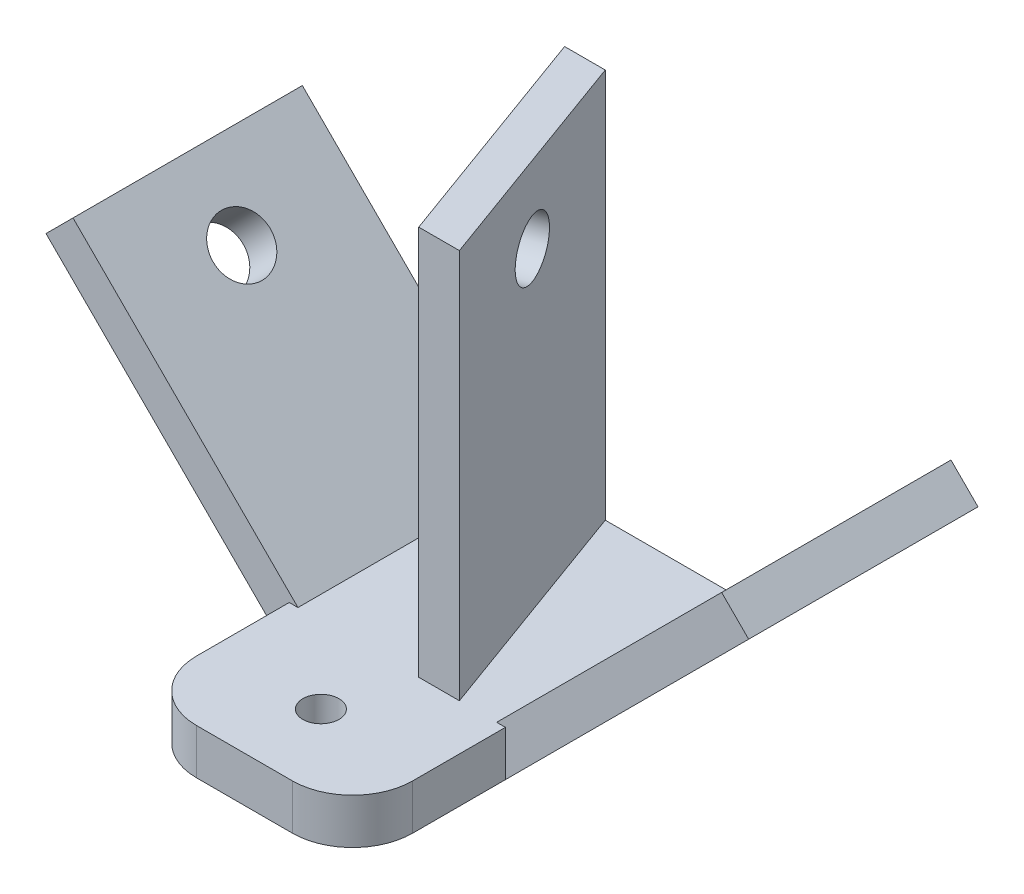
SolidWorks part; units mm, degrees
ref_plane "Front Plane" through (0, 0, 0) normal (0, 0, 1) x (1, 0, 0)
ref_plane "Top Plane" through (0, 0, 0) normal (0, 1, 0) x (1, 0, 0)
ref_plane "Right Plane" through (0, 0, 0) normal (1, 0, 0) x (0, 0, -1)
sketch "Sketch1" plane through (0, 0, 0) normal (0, 0, 1) x (1, 0, 0)
  line L0 (-53.8815, 53.8815) -> (0, 0)
  line L1 (0, 0) -> (53.8815, 53.8815)
  line L2 (53.8815, 53.8815) -> (58.3717, 49.3914)
  line L3 (58.3717, 49.3914) -> (0, -8.9803)
  line L4 (0, -8.9803) -> (-58.3717, 49.3914)
  line L5 (-58.3717, 49.3914) -> (-53.8815, 53.8815)
  line L6 (0, -8.9803) -> (0, 0) construction
  dimension "D1" = 6.35
  dimension "D2" = 76.2
extrude "Boss-Extrude1" add sketch "Sketch1" along normal mid plane 38.1
sketch "Sketch2" plane through (0, 0, 0) normal (0, 1, 0) x (1, 0, 0)
  line L0 (-10.3124, 19.05) -> (-3.5549, 19.05)
  line L1 (0, 19.05) -> (-53.8815, 19.05) construction
  line L2 (-3.5549, 19.05) -> (10.3124, -19.05)
  line L3 (53.8815, -19.05) -> (0, -19.05) construction
  line L4 (10.3124, -19.05) -> (3.5549, -19.05)
  line L5 (3.5549, -19.05) -> (-10.3124, 19.05)
  line L6 (-6.9336, 19.05) -> (6.9336, -19.05) construction
  line L7 (0, -19.05) -> (-53.8815, -19.05) construction
  point P10 (0, 0)
  dimension "D1" = 6.35
  dimension "D2" = 70
extrude "Boss-Extrude2" add sketch "Sketch2" against normal up to body and the other way blind 76.2 from offset 5.08 separate body
sketch "Sketch3" plane through (-4.4901, -4.4901, 0) normal (-0.7071, -0.7071, 0) x (0, 0, 1)
  line L0 (19.05, 76.2) -> (-19.05, 76.2) construction
  circle A0 centre (0, 63.5) radius 4.7625
  point P4 (0, 76.2)
  dimension "D1" = 9.525
  dimension "D2" = 12.7
extrude "Cut-Extrude1" cut sketch "Sketch3" against normal up to next
mirror "Mirror1" about plane through (0, 0, 0) normal (1, 0, 0) of "Cut-Extrude1"
sketch "Sketch4" plane through (2.9835, 0, -1.0859) normal (0.9397, 0, -0.342) x (-0.342, 0, -0.9397)
  line L0 (-21.4282, 81.28) -> (19.117, 81.28) construction
  circle A0 centre (-1.1556, 68.58) radius 4.7625
  point P4 (-1.1556, 81.28)
  dimension "D2" = 9.525
  dimension "D1" = 12.7
extrude "Cut-Extrude2" cut sketch "Sketch4" against normal up to next
sketch "Sketch5" plane through (0, 0, 19.05) normal (0, 0, 1) x (1, 0, 0)
  line L0 (-16.51, 16.51) -> (16.51, 16.51)
  line L1 (0, 0) -> (-53.8815, 53.8815) construction
  line L2 (53.8815, 53.8815) -> (10.3124, 10.3124) construction
  line L3 (16.51, 16.51) -> (0, 0)
  line L4 (0, 0) -> (-16.51, 16.51)
  dimension "D1" = 16.51
extrude "Boss-Extrude3" add sketch "Sketch5" against normal up to surface (38.1 mm away) up to face at (-2.7735, 37.3993, -19.05)
chamfer "Chamfer1" distance 25.4 angle 45 1 edges at (0, -8.9803, 0)
sketch "Sketch6" plane through (0, 8.9803, 0) normal (0, -1, 0) x (1, 0, 0)
  line L1 (-17.9605, 19.05) -> (17.9605, 19.05)
  line L2 (-17.9605, 19.05) -> (-17.9605, 44.45)
  line L3 (-17.9605, 44.45) -> (17.9605, 44.45)
  line L4 (17.9605, 19.05) -> (17.9605, 44.45)
  line L5 (-17.9605, 19.05) -> (17.9605, 44.45) construction
  line L6 (-17.9605, 44.45) -> (17.9605, 19.05) construction
  point P4 (0, 31.75)
  dimension "D1" = 25.4
extrude "Boss-Extrude4" add sketch "Sketch6" against normal up to surface (7.5297 mm away) up to face at (-9.9444, 16.51, 0)
sketch "Sketch7" plane through (0, 16.51, 0) normal (0, 1, 0) x (1, 0, 0)
  line L0 (-17.9605, -44.45) -> (-17.9605, -19.05) construction
  line L1 (17.9605, -44.45) -> (-17.9605, -44.45) construction
  circle A0 centre (0, -31.75) radius 3
  point P4 (-17.9605, -31.75)
  point P7 (0, -44.45)
  dimension "D1" = 6
extrude "Cut-Extrude3" cut sketch "Sketch7" against normal through all
fillet "Fillet1" radius 10 2 edges at (17.9605, 12.7451, 44.45) (-17.9605, 12.7451, 44.45)
